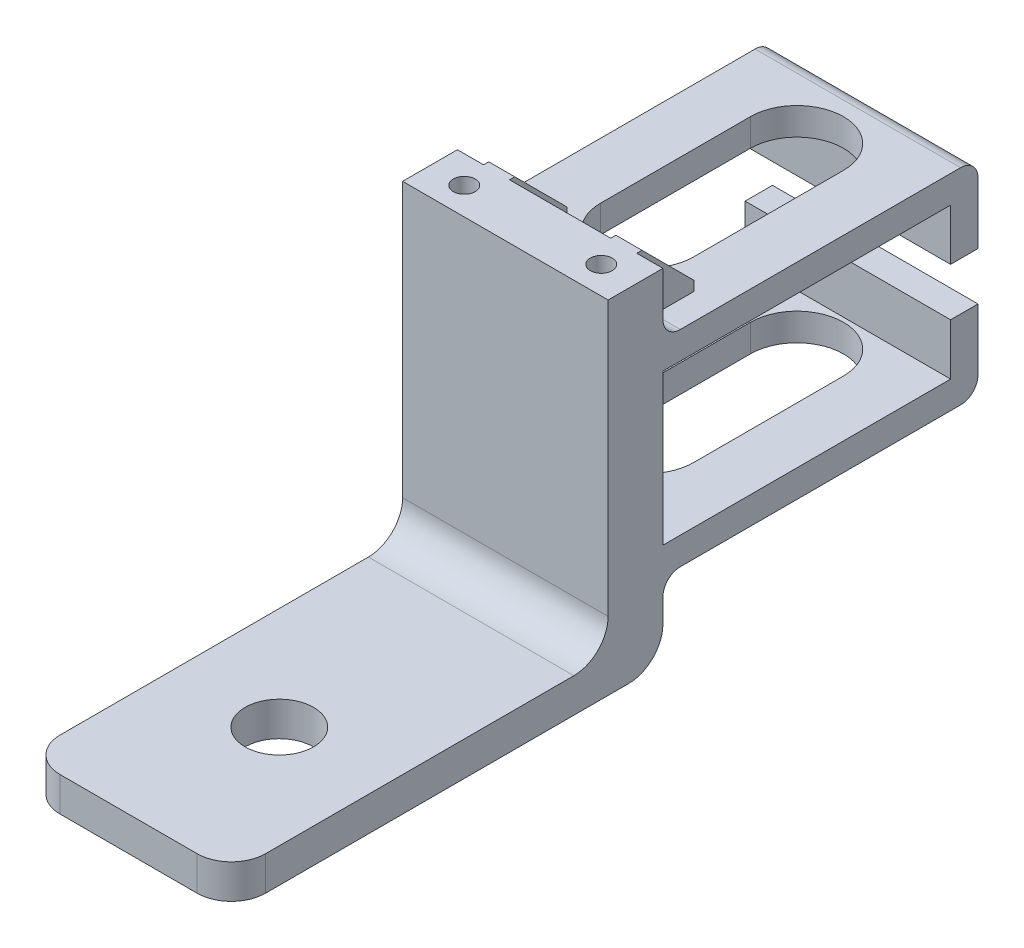
SolidWorks part; units mm, degrees
ref_plane "Front Plane" through (0, 0, 0) normal (0, 0, 1) x (1, 0, 0)
ref_plane "Top Plane" through (0, 0, 0) normal (0, 1, 0) x (1, 0, 0)
ref_plane "Right Plane" through (0, 0, 0) normal (1, 0, 0) x (0, 0, -1)
sketch "Sketch1" plane through (0, 0, 0) normal (1, 0, 0) x (0, 0, -1)
  line L1 (0, 0) -> (63, 0)
  line L2 (0, 0) -> (0, 5)
  line L3 (0, 5) -> (63, 5)
  line L4 (63, 0) -> (63, 5)
  dimension "D1" = 5
  dimension "D2" = 63
extrude "Boss-Extrude1" add sketch "Sketch1" along normal blind 30 contours L3 L4 L1 L2
sketch "Sketch2" plane through (0, 5, 0) normal (0, 1, 0) x (1, 0, 0)
  line L0 (30, 0) -> (30, 63) construction
  line L1 (0, 63) -> (30, 63)
  line L2 (0, 63) -> (0, 55)
  line L3 (0, 55) -> (30, 55)
  line L4 (30, 63) -> (30, 55)
  dimension "D1" = 8
extrude "Boss-Extrude2" add sketch "Sketch2" along normal blind 45
sketch "Sketch3" plane through (0, 5, 0) normal (0, 1, 0) x (1, 0, 0)
  line L0 (30, 0) -> (0, 0) construction
  circle A0 centre (15, 22) radius 5
  point P4 (15, 0)
  dimension "D2" = 10
  dimension "D1" = 22
extrude "Cut-Extrude1" cut sketch "Sketch3" against normal through all
sketch "Sketch5" plane through (0, 50, 0) normal (0, 1, 0) x (1, 0, 0)
  line L0 (0, 63) -> (0, 55) construction
  line L1 (30, 55) -> (30, 63) construction
  circle A0 centre (5, 59) radius 1.6
  circle A1 centre (25, 59) radius 1.6
  point P5 (0, 59)
  dimension "D1" = 3.2
  dimension "D3" = 5
  dimension "D2" = 5
extrude "Cut-Extrude3" cut sketch "Sketch5" against normal blind 14
fillet "Fillet1" radius 5 4 edges at (15, 0, -63) (15, 5, -55) (30, 2.5, 0) (0, 2.5, 0)
sketch "Sketch6" plane through (30, 0, 0) normal (1, 0, 0) x (0, 0, -1)
  line L0 (63, 5) -> (63, 50) construction
  line L1 (63, 37) -> (105, 37)
  line L2 (63, 37) -> (63, 15)
  line L3 (63, 15) -> (105, 15)
  line L4 (105, 37) -> (105, 15)
  line L5 (5, 0) -> (58, 0) construction
  line L6 (63, 41) -> (109, 41)
  line L7 (63, 41) -> (63, 11)
  line L8 (63, 11) -> (109, 11)
  line L9 (109, 41) -> (109, 11)
  line M11 (63, 5) -> (63, 50)
  dimension "D1" = 4
  dimension "D2" = 4
  dimension "D3" = 4
  dimension "D4" = 22
  dimension "D5" = 42
  dimension "D6" = 15
extrude "Boss-Extrude3" add sketch "Sketch6" against normal up to surface (30 mm away) contours L9 L6 L1 L4 L3 L8 M11 region at (30, 39, -63.5492) up to face at (0, 15.3661, -44.5089)
fillet "Fillet2" radius 2.54 4 edges at (15, 11, -109) (15, 11, -63) (15, 41, -63) (15, 41, -109)
sketch "Sketch8" plane through (0, 41, 0) normal (0, 1, 0) x (1, 0, 0)
  line L0 (15, 97.57) -> (15, 75.7) construction
  line L1 (21.7934, 97.57) -> (21.7934, 75.7)
  line L2 (8.2066, 97.57) -> (8.2066, 75.7)
  line L3 (0, 65.54) -> (30, 65.54) construction
  line L4 (30, 106.46) -> (0, 106.46) construction
  arc A0 (21.7934, 97.57) -> (8.2066, 97.57) centre (15, 97.57) ccw
  arc A1 (8.2066, 75.7) -> (21.7934, 75.7) centre (15, 75.7) ccw
  point P2 (15, 86.635)
  point P7 (15, 65.54)
  dimension "D1" = 8.89
  dimension "D2" = 10.16
extrude "Cut-Extrude5" cut sketch "Sketch8" against normal through all
sketch "Sketch9" plane through (0, 41, 0) normal (0, 1, 0) x (1, 0, 0)
  line L0 (30, 63) -> (0, 63) construction
  line L1 (3.81, 63) -> (7.62, 63)
  line L2 (3.81, 63) -> (3.81, 71.3781)
  line L3 (3.81, 71.3781) -> (7.62, 71.3781)
  line L4 (7.62, 63) -> (7.62, 71.3781)
  line L6 (22.38, 63) -> (26.19, 63)
  line L7 (22.38, 63) -> (22.38, 71.3781)
  line L8 (22.38, 71.3781) -> (26.19, 71.3781)
  line L9 (26.19, 63) -> (26.19, 71.3781)
  line L10 (30, 65.54) -> (30, 106.46) construction
  dimension "D1" = 3.81
  dimension "D3" = 3.81
extrude "Boss-Extrude4" add sketch "Sketch9" along normal up to surface (9 mm away) up to face at (5, 50, -57.4)
chamfer "Chamfer1" distance 7.62 angle 45 2 edges at (5.715, 50, -71.3781) (24.285, 50, -71.3781)
sketch "Sketch10" plane through (0, 11, 0) normal (0, -1, 0) x (1, 0, 0)
  line L1 (3.81, -63) -> (7.62, -63)
  line L2 (3.81, -63) -> (3.81, -71.3781)
  line L3 (3.81, -71.3781) -> (7.62, -71.3781)
  line L4 (7.62, -63) -> (7.62, -71.3781)
  line L5 (22.38, -63) -> (26.19, -63)
  line L6 (22.38, -63) -> (22.38, -71.3781)
  line L7 (22.38, -71.3781) -> (26.19, -71.3781)
  line L8 (26.19, -63) -> (26.19, -71.3781)
extrude "Boss-Extrude5" add sketch "Sketch10" along normal up to vertex (6 mm away) up to point (30, 5, -63)
chamfer "Chamfer2" distance 7.62 angle 45 2 edges at (24.285, 5, -71.3781) (5.715, 5, -71.3781)
ref_plane "Plane2" through (15, 0, 0) normal (1, 0, 0) x (0, 0, -1)
sketch "Sketch11" plane through (30, 0, 0) normal (1, 0, 0) x (0, 0, -1)
  line L0 (105, 37) -> (105, 15) construction
  line L1 (105, 29.5) -> (109, 29.5)
  line L2 (105, 29.5) -> (105, 22.5)
  line L3 (105, 22.5) -> (109, 22.5)
  line L4 (109, 29.5) -> (109, 22.5)
  line L5 (109, 38.46) -> (109, 13.54) construction
  point P8 (109, 26)
  point P9 (109, 26)
  point P10 (0, 0)
  dimension "D1" = 7
extrude "Cut-Extrude6" cut sketch "Sketch11" against normal through all
